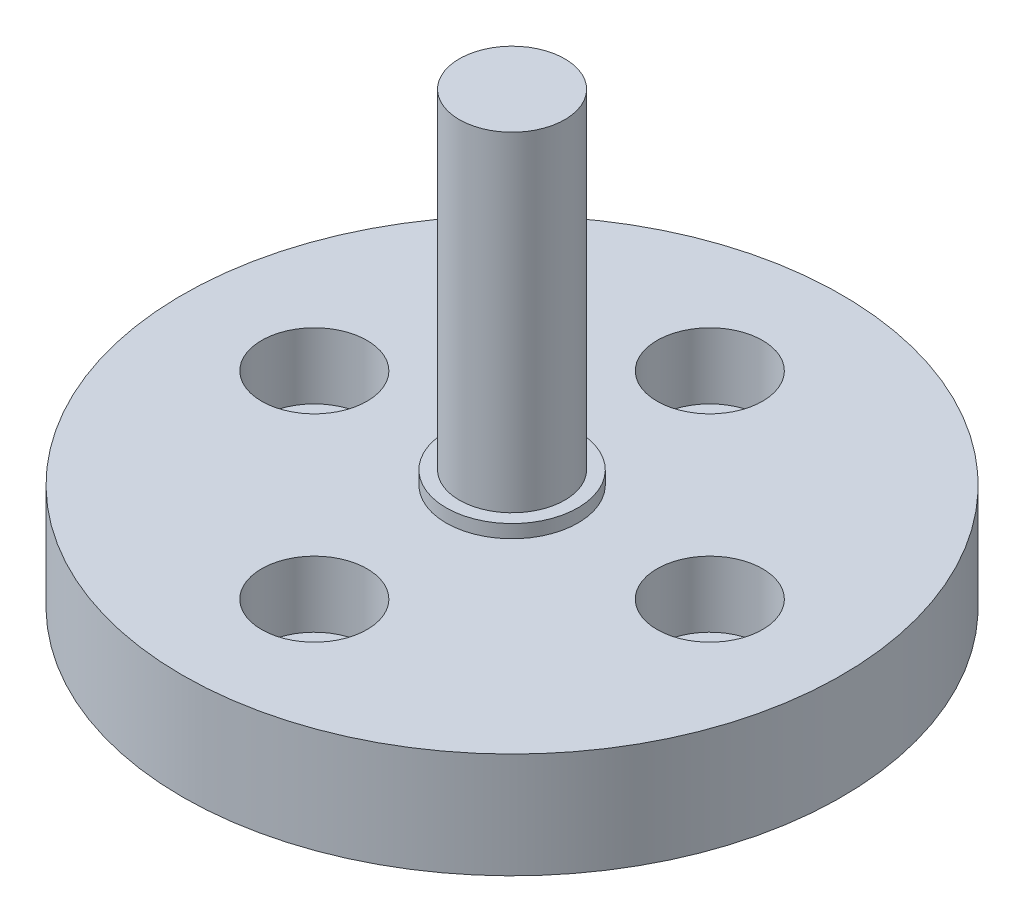
SolidWorks part; units mm, degrees
ref_plane "Front Plane" through (0, 0, 0) normal (0, 0, 1) x (1, 0, 0)
ref_plane "Top Plane" through (0, 0, 0) normal (0, 1, 0) x (1, 0, 0)
ref_plane "Right Plane" through (0, 0, 0) normal (1, 0, 0) x (0, 0, -1)
sketch "Sketch1" plane through (0, 0, 0) normal (0, 1, 0) x (1, 0, 0)
  circle A0 centre (0, 0) radius 25
  dimension "D1" = 50
extrude "Boss-Extrude1" add sketch "Sketch1" along normal blind 8
sketch "Sketch2" plane through (0, 8, 0) normal (0, 1, 0) x (1, 0, 0)
  circle A0 centre (0, 0) radius 5
  dimension "D1" = 10
extrude "Boss-Extrude2" add sketch "Sketch2" along normal blind 1
sketch "Sketch3" plane through (0, 9, 0) normal (0, 1, 0) x (1, 0, 0)
  circle A0 centre (0, 0) radius 4
  dimension "D1" = 8
extrude "Boss-Extrude3" add sketch "Sketch3" along normal blind 15
hole_wizard "Hole1" positions "Sketch7" profile "Sketch6" legacy end condition through all
sketch "Sketch7" plane through (0, 8, 0) normal (0, 1, 0) x (1, 0, 0)
  point P0 (-15, 0)
  point P2 (0, 15)
  point P4 (15, 0)
  point P6 (0, -15)
  dimension "D1" = 15
  dimension "D2" = 15
  dimension "D3" = 15
  dimension "D4" = 15
sketch "Sketch6" plane through (-15, 8, 0) normal (1, 0, 0) x (0, 0, 1)
  line L0 (0, 0) -> (0, 8)
  line L1 (0, 8) -> (2, 8)
  line L2 (2, 8) -> (2, 5)
  line L3 (2, 5) -> (4, 5)
  line L4 (4, 5) -> (4, 0)
  line L5 (4, 0) -> (0, 0)
  line L6 (0, 110) -> (0, -10) construction
  dimension "Diameter" = 4
  dimension "Depth" = 8
  dimension "C-Bore Diameter" = 8
  dimension "C-Bore Depth" = 5
sketch "Sketch8" plane through (0, 24, 0) normal (0, 1, 0) x (1, 0, 0)
  circle A0 centre (0, 0) radius 4
extrude "Boss-Extrude4" add sketch "Sketch8" along normal blind 10
